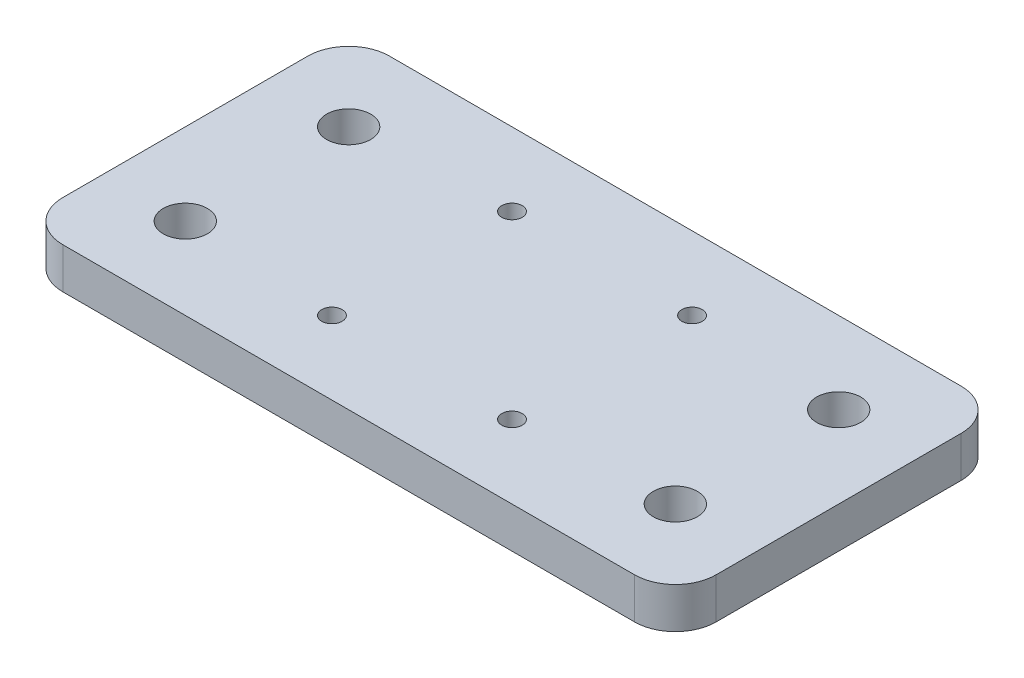
SolidWorks part; units mm, degrees
material "6061 Alloy"
ref_plane "Front Plane" through (0, 0, 0) normal (0, 0, 1) x (1, 0, 0)
ref_plane "Top Plane" through (0, 0, 0) normal (0, 1, 0) x (1, 0, 0)
ref_plane "Right Plane" through (0, 0, 0) normal (1, 0, 0) x (0, 0, -1)
sketch "Sketch1" plane through (0, 0, 0) normal (0, 1, 0) x (1, 0, 0)
  line L1 (-50.8, 25.4) -> (50.8, 25.4)
  line L2 (-50.8, 25.4) -> (-50.8, -25.4)
  line L3 (-50.8, -25.4) -> (50.8, -25.4)
  line L4 (50.8, 25.4) -> (50.8, -25.4)
  line L5 (-50.8, 25.4) -> (50.8, -25.4) construction
  line L6 (-50.8, -25.4) -> (50.8, 25.4) construction
  point P0 (0, 0)
  dimension "D1" = 50.8
  dimension "D2" = 101.6
extrude "Boss-Extrude1" add sketch "Sketch1" along normal blind 6.35
sketch "Sketch3" plane through (0, 0, 0) normal (0, -1, 0) x (1, 0, 0)
  line L0 (0, 0) -> (0, -20.7585) construction
  line L1 (0, 0) -> (-13.1006, 0) construction
  line L2 (-50.8, -25.4) -> (-50.8, 25.4) construction
  line L3 (-50.8, 25.4) -> (50.8, 25.4) construction
  line L4 (50.8, -25.4) -> (-50.8, -25.4) construction
  circle A0 centre (-38.1, 12.7) radius 3.429
  circle A1 centre (-38.1, -12.7) radius 3.429
  circle A2 centre (38.1, 12.7) radius 3.429
  circle A3 centre (38.1, -12.7) radius 3.429
  circle A4 centre (14, -14) radius 1.5875
  circle A5 centre (-14, -14) radius 1.5875
  circle A6 centre (14, 14) radius 1.5875
  circle A7 centre (-14, 14) radius 1.5875
  dimension "D1" = 12.7
  dimension "D4" = 36.8
  dimension "D8" = 11.4
  dimension "D2" = 12.7
  dimension "D3" = 12.7
extrude "Cut-Extrude2" cut sketch "Sketch3" against normal up to next
fillet "Fillet1" radius 6.35 4 edges at (-50.8, 3.175, -25.4) (50.8, 3.175, -25.4) (50.8, 3.175, 25.4) (-50.8, 3.175, 25.4)
